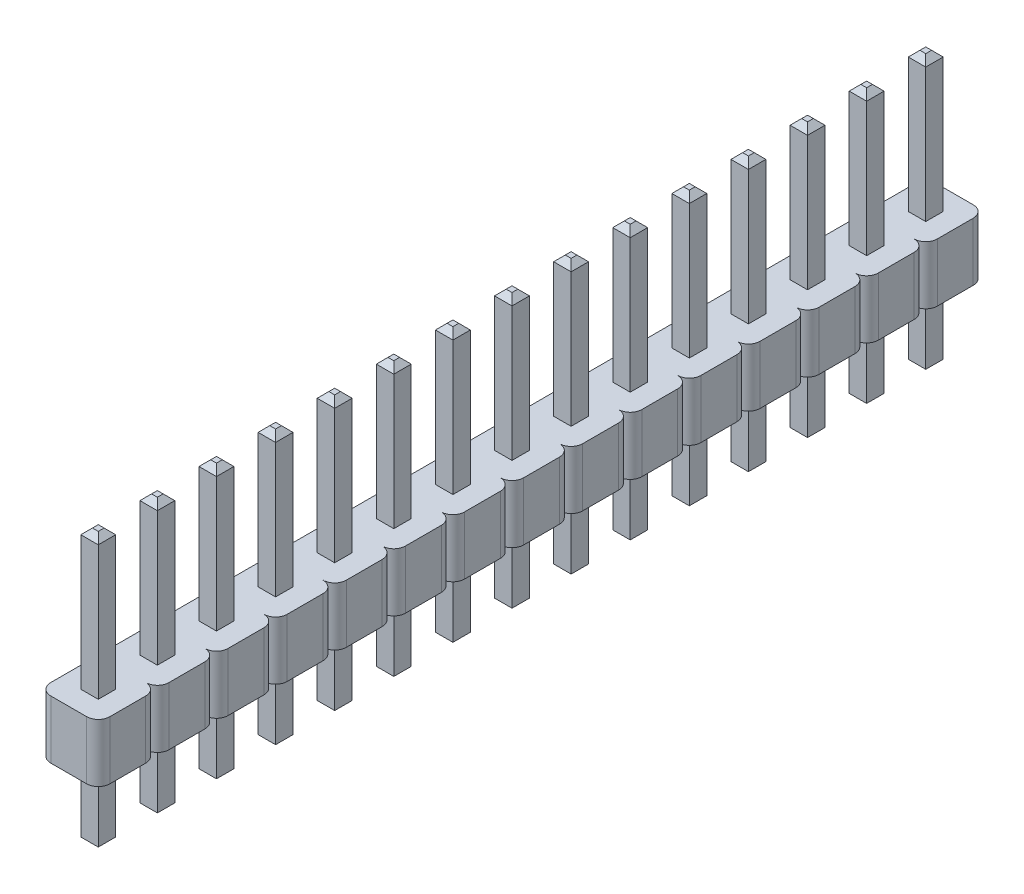
SolidWorks part; units mm, degrees
material "普通碳钢"
ref_plane "Front Plane" through (0, 0, 0) normal (0, 0, 1) x (1, 0, 0)
ref_plane "Top Plane" through (0, 0, 0) normal (0, 1, 0) x (1, 0, 0)
ref_plane "Right Plane" through (0, 0, 0) normal (1, 0, 0) x (0, 0, -1)
ref_plane "Plane1" through (0, 0, 0) normal (0, 1, 0) x (-1, 0, 0)
sketch "Sketch1" plane through (0, 0, 0) normal (0, 1, 0) x (-1, 0, 0)
  line L0 (-0.77, 1.27) -> (0.77, 1.27)
  line L1 (1.27, 0.77) -> (1.27, -0.77)
  line L2 (0.77, -1.27) -> (-0.77, -1.27)
  line L3 (-1.27, -0.77) -> (-1.27, 0.77)
  line L4 (-0.77, 0.77) -> (0.77, -0.77) construction
  arc A0 (1.27, 0.77) -> (0.77, 1.27) centre (0.77, 0.77) ccw
  arc A1 (0.77, -1.27) -> (1.27, -0.77) centre (0.77, -0.77) ccw
  arc A2 (-1.27, -0.77) -> (-0.77, -1.27) centre (-0.77, -0.77) ccw
  arc A3 (-0.77, 1.27) -> (-1.27, 0.77) centre (-0.77, 0.77) ccw
  dimension "D3" = 0.5
  dimension "D2" = 2.54
extrude "Boss-Extrude1" add sketch "Sketch1" along normal blind 2.5
ref_plane "Plane2" through (0.77, 0, 1.27) normal (-1, 0, 0) x (0, 0, 1)
ref_plane "Plane3" through (0.77, 0, 1.27) normal (0, -1, 0) x (0, 0, 1)
ref_axis "Axis1" through (0.77, 0, -79.63) along (0, 0, 1)
pattern_linear "LPattern1" count 15 spacing 2.54 along (0, 0, 1) of "Boss-Extrude1"
ref_plane "Plane4" through (0, 0, 0) normal (0, 1, 0) x (-1, 0, 0)
sketch "Sketch2" plane through (0, 0, 0) normal (0, 1, 0) x (-1, 0, 0)
  line L0 (-0.375, 0.375) -> (0.375, 0.375)
  line L1 (0.375, 0.375) -> (0.375, -0.375)
  line L2 (0.375, -0.375) -> (-0.375, -0.375)
  line L3 (-0.375, -0.375) -> (-0.375, 0.375)
  line L4 (-0.375, 0.375) -> (0.375, -0.375) construction
  dimension "D1" = 0.75
extrude "Boss-Extrude2" add sketch "Sketch2" along normal blind 8.5 and the other way blind 3.25
ref_plane "Plane5" through (0.3725, 0, 0.3725) normal (-1, 0, 0) x (0, 0, 1)
ref_plane "Plane6" through (0.3725, 0, 0.3725) normal (0, -1, 0) x (0, 0, 1)
ref_axis "Axis2" through (0.3725, 0, -80.5275) along (0, 0, 1)
chamfer "Chamfer1" distance 0.25 angle 45 8 edges at (0, -3.25, 0.375) (-0.375, -3.25, 0) (0.375, -3.25, 0) (0, -3.25, -0.375) (0, 8.5, 0.375) (-0.375, 8.5, 0) (0, 8.5, -0.375) (0.375, 8.5, 0)
pattern_linear "LPattern2" count 15 spacing 2.54 along (0, 0, 1) of "Boss-Extrude2", "Chamfer1"
ref_axis "Axis3" through (0, -3.575, 0) along (0, 1, 0)
